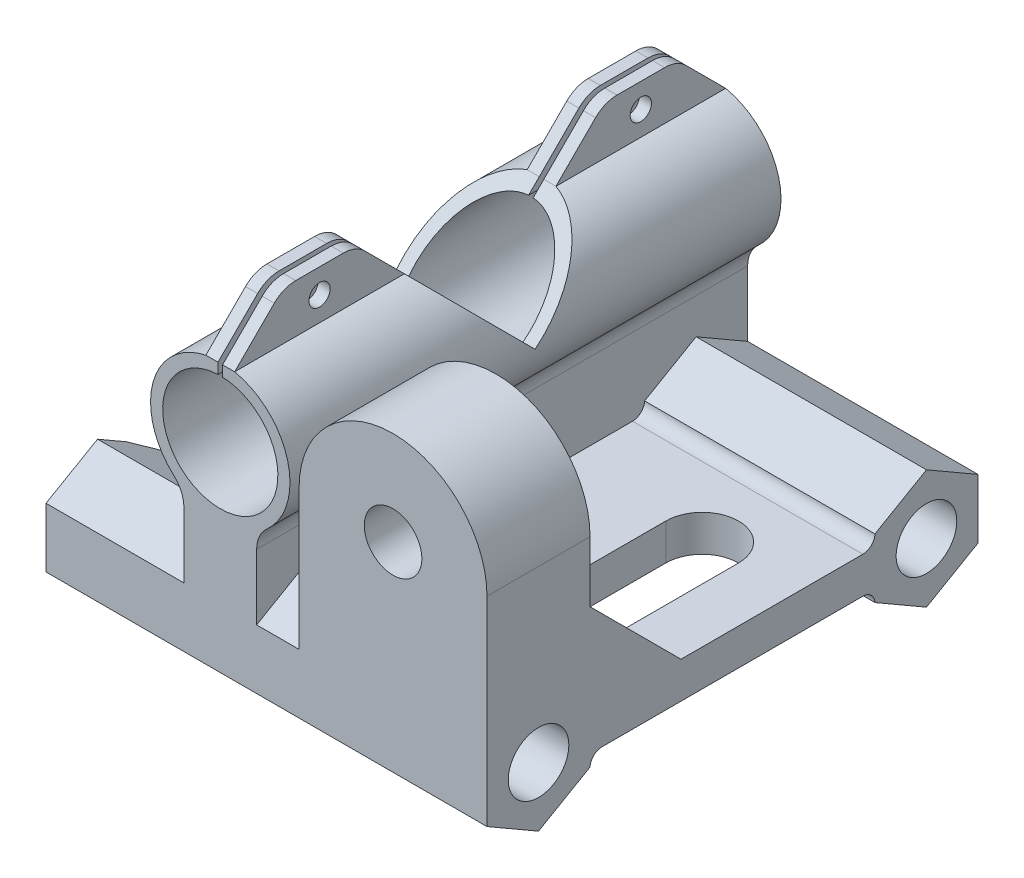
SolidWorks part; units mm, degrees
ref_plane "Front Plane" through (0, 0, 0) normal (0, 0, 1) x (1, 0, 0)
ref_plane "Top Plane" through (0, 0, 0) normal (0, 1, 0) x (1, 0, 0)
ref_plane "Right Plane" through (0, 0, 0) normal (1, 0, 0) x (0, 0, -1)
sketch "Sketch2" plane through (0, 0, 0) normal (1, 0, 0) x (0, 0, -1)
  line L0 (-5.6113, 0) -> (58.3887, 0) construction
  line L1 (2.8887, 3) -> (49.8887, 3)
  line L2 (66.8887, 4.9075) -> (58.3887, 9.815)
  line L3 (58.3887, 9.815) -> (49.8887, 4.9075)
  line L4 (49.8887, 4.9075) -> (49.8887, 3)
  line L5 (49.8887, -4.9075) -> (58.3887, -9.815)
  line L6 (58.3887, -9.815) -> (66.8887, -4.9075)
  line L7 (66.8887, -4.9075) -> (66.8887, 4.9075)
  line L8 (2.8887, 4.9075) -> (-5.6113, 9.815)
  line L9 (-5.6113, 9.815) -> (-14.1113, 4.9075)
  line L10 (-14.1113, 4.9075) -> (-14.1113, -4.9075)
  line L11 (-14.1113, -4.9075) -> (-5.6113, -9.815)
  line L12 (-5.6113, -9.815) -> (2.8887, -4.9075)
  line L13 (2.8887, -4.9075) -> (2.8887, -3)
  line L14 (2.8887, -3) -> (49.8887, -3)
  line L15 (49.8887, -3) -> (49.8887, -4.9075)
  line L16 (2.8887, 3) -> (2.8887, 4.9075)
  circle A2 centre (58.3887, 0) radius 8.5 construction
  circle A3 centre (-5.6113, 0) radius 8.5 construction
  dimension "D2" = 17
  dimension "D3" = 47
  dimension "D4" = 6
  dimension "D5" = 3
extrude "Boss-Extrude1" add sketch "Sketch2" along normal blind 72.75
sketch "Sketch3" plane through (0, 3, 0) normal (0, 1, 0) x (1, 0, 0)
  line L0 (0, 49.8887) -> (47, 2.8887) construction
  line L1 (72.75, 2.8887) -> (0, 2.8887) construction
  line L2 (0, 2.8887) -> (47, 49.8887) construction
  line L3 (72.75, 49.8887) -> (0, 49.8887) construction
  line L4 (72.75, 2.8887) -> (0, 2.8887) construction
  line L5 (1.75, 48.1387) -> (1.75, 2.8887)
  line L6 (39, 41.8887) -> (8, 41.8887) construction
  line L7 (39, 41.8887) -> (39, 10.8887) construction
  line L8 (39, 10.8887) -> (8, 10.8887) construction
  line L9 (8, 41.8887) -> (8, 10.8887) construction
  line L10 (1.75, 48.1387) -> (45.25, 48.1387) construction
  line L11 (45.25, 48.1387) -> (45.25, 4.6387) construction
  line L12 (45.25, 4.6387) -> (1.75, 4.6387) construction
  line L13 (1.75, 2.8887) -> (0, -0.8613)
  line L14 (0, 2.8887) -> (0, -5.6113) construction
  line L16 (1.75, 48.1387) -> (1.75, 49.8887)
  line L18 (1.75, 49.8887) -> (0, 51.6387)
  line L20 (0, 58.3887) -> (0, 49.8887) construction
  line L21 (0, 51.6387) -> (0, -0.8613)
  dimension "D1" = 45
  dimension "D2" = 45
  dimension "D3" = 31
  dimension "D6" = 43.5
extrude "Cut-Extrude1" cut sketch "Sketch3" against normal blind 28 and the other way blind 30
fillet "Fillet3" radius 2 4 edges at (37.25, -3, -2.8887) (37.25, -3, -49.8887) (37.25, 3, -49.8887) (37.25, 3, -2.8887)
sketch "Sketch4" plane through (0, 0, -66.8887) normal (0, 0, -1) x (-1, 0, 0)
  line L0 (-28.75, 3) -> (-28.75, 28) construction
  line L1 (-72.75, 3) -> (-1.75, 3) construction
  line L3 (-34.75, 3) -> (-34.75, 18.1893)
  line L4 (-22.75, 3) -> (-22.75, 18.1893)
  line L5 (-22.75, 3) -> (-34.75, 3)
  line L6 (-26.375, 39.2521) -> (-26.375, 47.2521)
  line L7 (-26.375, 47.2521) -> (-28.375, 47.2521)
  line L8 (-28.375, 47.2521) -> (-28.375, 37.4926)
  line L9 (-31.125, 39.2521) -> (-31.125, 47.2521)
  line L10 (-31.125, 47.2521) -> (-29.125, 47.2521)
  line L11 (-29.125, 47.2521) -> (-29.125, 37.4926)
  line L12 (-1.75, 4.9075) -> (-1.75, -4.9075) construction
  arc A0 (-29.125, 37.4926) -> (-28.375, 37.4926) centre (-28.75, 28) ccw
  arc A1 (-22.75, 18.1893) -> (-26.375, 39.2521) centre (-28.75, 28) ccw
  arc A3 (-31.125, 39.2521) -> (-34.75, 18.1893) centre (-28.75, 28) ccw
  dimension "D1" = 2
  dimension "D2" = 2
  dimension "D3" = 0.75
  dimension "D10" = 8
  dimension "D6" = 19
  dimension "D7" = 23
  dimension "D4" = 12
  dimension "D5" = 6
  dimension "D8" = 25
  dimension "D9" = 0.375
  dimension "D11" = 27
extrude "Boss-Extrude2" add sketch "Sketch4" against normal up to surface (81 mm away) up to face at (36.375, 0, 14.1113)
fillet "Fillet4" radius 5 2 edges at (22.75, 18.1893, -26.3887) (34.75, 18.1893, -26.3887)
sketch "Sketch5" plane through (0, 0, 14.1113) normal (0, 0, -1) x (-1, 0, 0)
  line L0 (-28.75, 28) -> (-110, 28) construction
  line L1 (-72.75, 28) -> (-72.75, 4.9075)
  line L2 (-72.75, 4.9075) -> (-34.75, 4.9075) construction
  line L3 (-72.75, 4.9075) -> (-41.75, 4.9075)
  line L4 (-41.75, 4.9075) -> (-41.75, 28)
  circle A0 centre (-57.25, 28) radius 4.75
  arc A1 (-41.75, 28) -> (-72.75, 28) centre (-57.25, 28) ccw
  arc A2 (-29.125, 37.4926) -> (-28.375, 37.4926) centre (-28.75, 28) ccw construction
  dimension "D1" = 9.5
  dimension "D3" = 31
  dimension "D4" = 0
  dimension "D5" = 28.5
  dimension "D2" = 28.5
extrude "Boss-Extrude7" add sketch "Sketch5" along normal up to vertex (17 mm away) up to point (72.75, 4.9075, -2.8887)
sketch "Sketch6" plane through (0, 0, -2.8887) normal (0, 0, -1) x (-1, 0, 0)
  line L0 (-41.75, 9.815) -> (-34.75, 9.815) construction
  line L1 (-49.7444, 28) -> (-53.4972, 34.5)
  line L2 (-53.4972, 34.5) -> (-61.0028, 34.5)
  line L3 (-61.0028, 34.5) -> (-64.7556, 28)
  line L4 (-64.7556, 28) -> (-61.0028, 21.5)
  line L5 (-61.0028, 21.5) -> (-53.4972, 21.5)
  line L6 (-53.4972, 21.5) -> (-49.7444, 28)
  circle A0 centre (-57.25, 28) radius 6.5 construction
  dimension "D1" = 13
extrude "Cut-Extrude2" cut sketch "Sketch6" against normal blind 7.5
sketch "Sketch7" plane through (0, 0, 0) normal (-1, 0, 0) x (0, 0, 1)
  line L0 (14.1113, 47.2521) -> (-66.8887, 47.2521) construction
  line L1 (-66.8887, 39.2521) -> (-38.8887, 39.2521) construction
  line L2 (-66.8887, 39.2521) -> (-66.8887, 19.4284) construction
  line L3 (-66.8887, 19.4284) -> (-38.8887, 19.4284) construction
  line L4 (-38.8887, 39.2521) -> (-38.8887, 19.4284) construction
  line L6 (14.1113, 19.4284) -> (-13.8887, 19.4284) construction
  line L7 (14.1113, 19.4284) -> (14.1113, 39.2521) construction
  line L8 (14.1113, 39.2521) -> (-13.8887, 39.2521) construction
  line L9 (-13.8887, 19.4284) -> (-13.8887, 39.2521) construction
  line L10 (14.1113, 43.2521) -> (-67.3887, 43.2521) construction
  line L11 (14.1113, 19.4284) -> (14.1113, 39.2521) construction
  line L12 (-38.8887, 47.2521) -> (-66.8887, 47.2521) construction
  line L13 (-52.8887, 39.2521) -> (-52.8887, 47.2521) construction
  line L15 (0.1113, 39.2521) -> (0.1113, 47.2521) construction
  line L16 (-38.8887, 39.2521) -> (-26.3887, 26.7521)
  line L17 (-13.8887, 39.2521) -> (-26.3887, 26.7521)
  line L18 (-13.8887, 39.2521) -> (-13.8887, 47.2521)
  line L19 (-38.8887, 39.2521) -> (-38.8887, 47.2521)
  line L20 (-38.8887, 47.2521) -> (-13.8887, 47.2521)
  line L21 (-66.8887, 19.4284) -> (14.1113, 19.4284) construction
  line L22 (-13.8887, 47.2521) -> (14.1113, 47.2521) construction
  line L25 (14.1113, 47.2521) -> (14.1113, 39.2521) construction
  line L26 (14.1113, 39.2521) -> (-66.8887, 39.2521) construction
  circle A0 centre (0.1113, 43.2521) radius 1.75
  circle A1 centre (-52.8887, 43.2521) radius 1.75
  dimension "D3" = 3.5
  dimension "D1" = 28
  dimension "D2" = 28
  dimension "D4" = 45
  dimension "D5" = 45
extrude "Cut-Extrude3" cut sketch "Sketch7" against normal up to surface (41.75 mm away) up to face at (41.75, 15.126, 5.6113)
chamfer "Chamfer1" distance 8 angle 45 8 edges at (27.375, 47.2521, -66.8887) (30.125, 47.2521, -66.8887) (30.125, 47.2521, -38.8887) (27.375, 47.2521, -38.8887) (30.125, 47.2521, 14.1113) (27.375, 47.2521, 14.1113) (27.375, 47.2521, -13.8887) (30.125, 47.2521, -13.8887)
fillet "Fillet5" radius 5 8 edges at (27.375, 47.2521, 6.1113) (30.125, 47.2521, 6.1113) (30.125, 47.2521, -5.8887) (27.375, 47.2521, -5.8887) (27.375, 47.2521, -46.8887) (30.125, 47.2521, -46.8887) (30.125, 47.2521, -58.8887) (27.375, 47.2521, -58.8887)
sketch "Sketch9" plane through (72.75, 0, 0) normal (1, 0, 0) x (0, 0, -1)
  line L0 (-9.8613, 7.3612) -> (-1.3613, -7.3612) construction
  line L1 (-5.6113, 9.815) -> (-14.1113, 4.9075) construction
  line L2 (-5.6113, -9.815) -> (2.8887, -4.9075) construction
  line L3 (54.1387, -7.3612) -> (62.6387, 7.3612) construction
  line L4 (49.8887, -4.9075) -> (58.3887, -9.815) construction
  circle A0 centre (58.3887, 0) radius 5
  circle A1 centre (-5.6113, 0) radius 5
  dimension "D1" = 10
extrude "Cut-Extrude5" cut sketch "Sketch9" against normal up to surface (50 mm away) up to face at (22.75, 7.5862, -26.3887)
sketch "Sketch14" plane through (0, 3, 0) normal (0, 1, 0) x (1, 0, 0)
  line L0 (57.75, 64.8887) -> (57.75, -14.1113) construction
  line L3 (72.75, 47.8909) -> (72.75, 4.8866) construction
  line L4 (57.75, 36.3887) -> (57.75, 14.3887) construction
  line L5 (63.75, 36.3887) -> (63.75, 14.3887)
  line L6 (51.75, 36.3887) -> (51.75, 14.3887)
  line L8 (41.75, -14.1113) -> (34.75, -14.1113) construction
  arc A0 (63.75, 36.3887) -> (51.75, 36.3887) centre (57.75, 36.3887) ccw
  arc A1 (51.75, 14.3887) -> (63.75, 14.3887) centre (57.75, 14.3887) ccw
  point P10 (57.75, 25.3887)
  dimension "D2" = 6
  dimension "D1" = 15
  dimension "D3" = 22
extrude "Cut-Extrude8" cut sketch "Sketch14" against normal blind 10
sketch "Sketch18" plane through (72.75, 0, 0) normal (1, 0, 0) x (0, 0, -1)
  line L0 (2.8941, 18) -> (2.8941, 3)
  line L1 (2.8941, 3) -> (17.8941, 3)
  line L2 (47.8909, 3) -> (4.8866, 3) construction
  line L3 (17.8941, 3) -> (2.8941, 18)
  dimension "D1" = 15
extrude "Boss-Extrude10" add sketch "Sketch18" against normal blind 3.5
sketch "Sketch19" plane through (41.75, 0, 0) normal (-1, 0, 0) x (0, 0, 1)
  line L0 (-2.8941, 18) -> (-17.8941, 3)
  line L1 (-17.8941, 3) -> (-2.8887, 3)
  line L2 (-2.8887, 4.9075) -> (-2.8887, -4.9075) construction
  line L3 (-2.8887, 3) -> (-2.8941, 18)
extrude "Boss-Extrude11" add sketch "Sketch19" against normal blind 3.5
